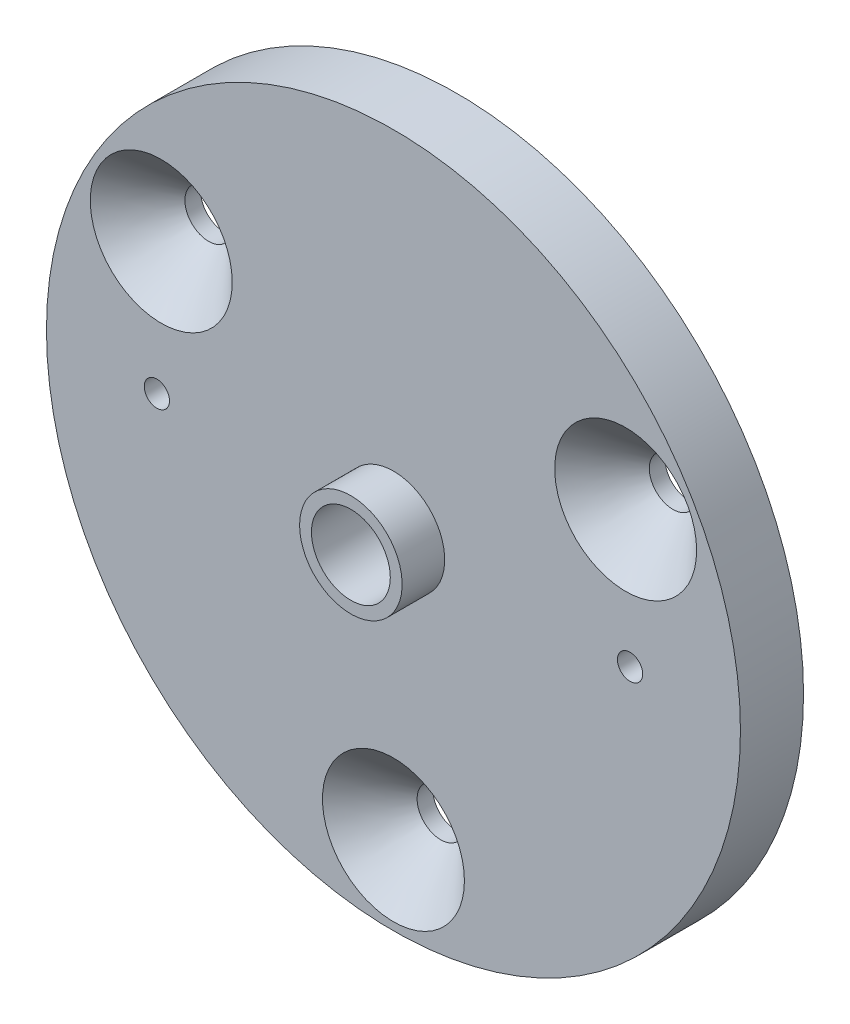
SolidWorks part; units mm, degrees
ref_plane "Спереди" through (0, 0, 0) normal (0, 0, 1) x (1, 0, 0)
ref_plane "Сверху" through (0, 0, 0) normal (0, 1, 0) x (1, 0, 0)
ref_plane "Справа" through (0, 0, 0) normal (1, 0, 0) x (0, 0, -1)
sketch "Эскиз1" plane through (0, 0, 0) normal (0, 0, 1) x (1, 0, 0)
  circle A0 centre (0, 0) radius 22
  dimension "D1" = 44
extrude "Бобышка-Вытянуть1" add sketch "Эскиз1" along normal blind 4
sketch "Эскиз2" plane through (0, 0, 4) normal (0, 0, 1) x (1, 0, 0)
  circle A0 centre (0, 0) radius 3.25
  dimension "D1" = 6.5
extrude "Бобышка-Вытянуть2" add sketch "Эскиз2" along normal blind 2.7
sketch "Эскиз3" plane through (0, 0, 6.7) normal (0, 0, 1) x (1, 0, 0)
  circle A0 centre (0, 0) radius 2.5
  dimension "D1" = 5
extrude "Вырез-Вытянуть1" cut sketch "Эскиз3" against normal through all
sketch "Эскиз4" plane through (0, 0, 4) normal (0, 0, 1) x (1, 0, 0)
  line L0 (-15, 0) -> (15, 0) construction
  circle A0 centre (-15, 0) radius 0.8
  circle A1 centre (15, 0) radius 0.8
  dimension "D1" = 1.6
  dimension "D2" = 15
  dimension "D3" = 30
  dimension "D4" = 15
extrude "Вырез-Вытянуть2" cut sketch "Эскиз4" against normal through all
sketch "Эскиз5" plane through (0, 0, 0) normal (0, 0, -1) x (-1, 0, 0)
  circle A0 centre (0, 0) radius 13
  dimension "D1" = 26
extrude "Вырез-Вытянуть3" cut sketch "Эскиз5" against normal blind 2.2
sketch "Эскиз6" plane through (0, 0, 4) normal (0, 0, 1) x (1, 0, 0)
  circle A0 centre (0, -17) radius 1.5
  circle A1 centre (-14.7224, 8.5) radius 1.5
  circle A2 centre (14.7224, 8.5) radius 1.5
  point P9 (0, 0)
  dimension "D1" = 3
  dimension "D2" = 0
  dimension "D3" = 17
  dimension "D4" = 3
extrude "Вырез-Вытянуть4" cut sketch "Эскиз6" against normal through all
chamfer "Фаска1" distance 3 angle 45 3 edges at (1.5, -17, 4) (16.2224, 8.5, 4) (-13.2224, 8.5, 4)
